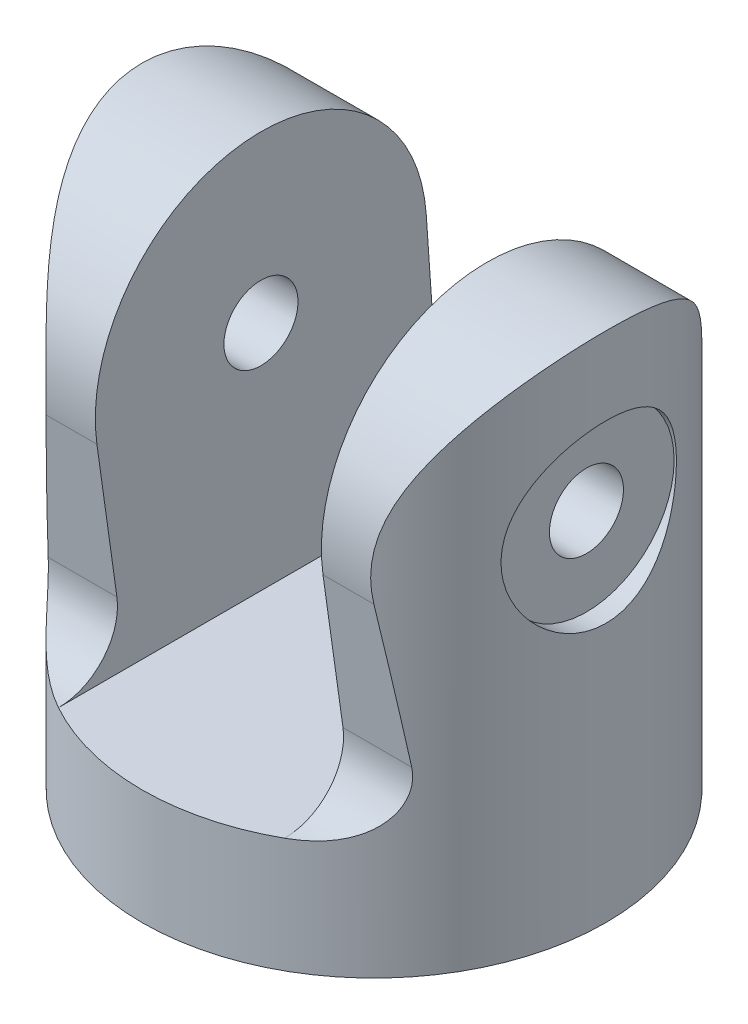
SolidWorks part; units mm, degrees
ref_plane "Front Plane" through (0, 0, 0) normal (0, 0, 1) x (1, 0, 0)
ref_plane "Top Plane" through (0, 0, 0) normal (0, 1, 0) x (1, 0, 0)
ref_plane "Right Plane" through (0, 0, 0) normal (1, 0, 0) x (0, 0, -1)
sketch "Sketch1" plane through (0, 0, 0) normal (0, 1, 0) x (1, 0, 0)
  circle A0 centre (0, 0) radius 119
  dimension "D1" = 238
extrude "Boss-Extrude1" add sketch "Sketch1" along normal blind 59 contours A0
ref_plane "Plane1" through (58, 0, 0) normal (1, 0, 0) x (0, 0, -1)
sketch "Sketch2" plane through (58, 0, 0) normal (1, 0, 0) x (0, 0, -1)
  line L0 (-84.1728, 166.1703) -> (-69.111, 59)
  line L1 (119, 59) -> (-119, 59) construction
  line L2 (84.7929, 183.9293) -> (93.5289, 59)
  line L3 (-69.111, 59) -> (93.5289, 59)
  arc A0 (84.7929, 183.9293) -> (-84.1728, 166.1703) centre (0, 178) ccw
  dimension "D1" = 170
  dimension "D2" = 178
  dimension "D3" = 98
  dimension "D4" = 86
extrude "Boss-Extrude2" add sketch "Sketch2" along normal up to surface (15.5755 mm away)
fillet "Fillet1" radius 30 1 edges at (77.4373, 59, 69.111)
fillet "Fillet4" radius 10 1 edges at (65.7877, 59, -93.5289)
mirror "Mirror1" about plane through (0, 0, 0) normal (1, 0, 0) of "Boss-Extrude2", "Fillet4", "Fillet1"
ref_plane "Plane3" through (119, 0, 0) normal (1, 0, 0) x (0, 0, -1)
sketch "Sketch8" plane through (119, 0, 0) normal (1, 0, 0) x (0, 0, -1)
  circle A0 centre (0, 178) radius 45
extrude "Cut-Extrude1" cut sketch "Sketch8" against normal blind 10
mirror "Mirror2" about plane through (0, 0, 0) normal (1, 0, 0) of "Cut-Extrude1"
sketch "Sketch10" plane through (119, 0, 0) normal (1, 0, 0) x (0, 0, -1)
  circle A0 centre (0, 178) radius 19
extrude "Cut-Extrude2" cut sketch "Sketch10" against normal blind 500
